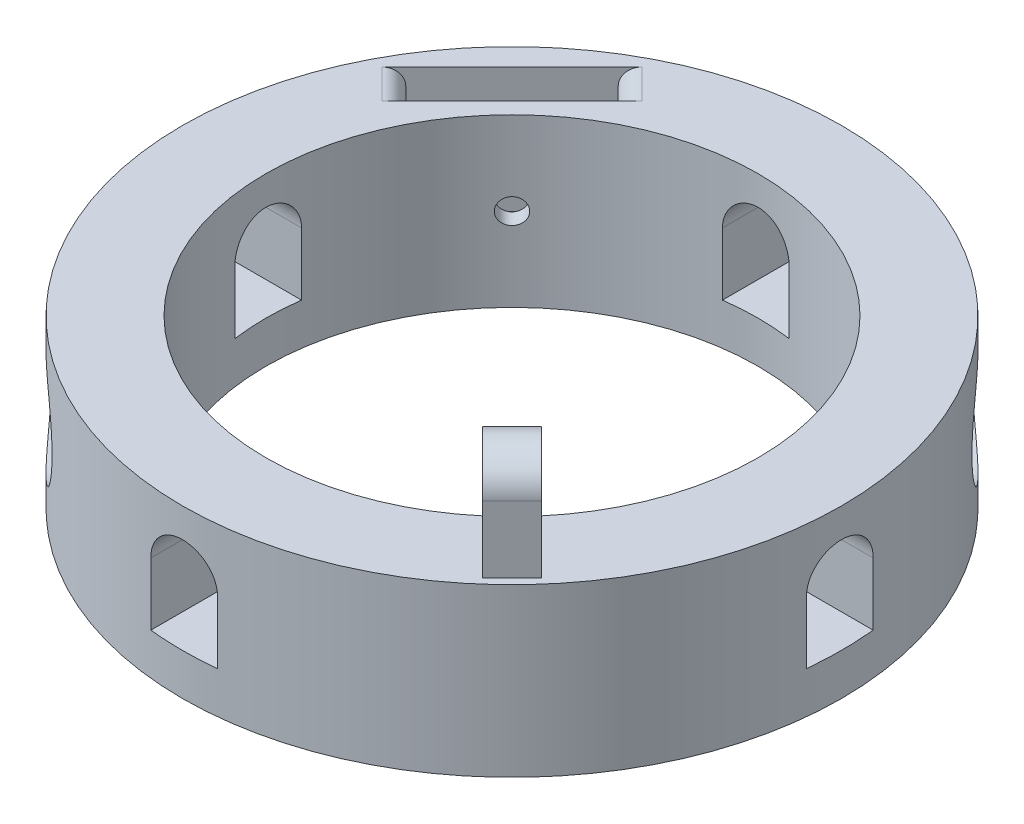
SolidWorks part; units mm, degrees
ref_plane "Front Plane" through (0, 0, 0) normal (0, 0, 1) x (1, 0, 0)
ref_plane "Top Plane" through (0, 0, 0) normal (0, 1, 0) x (1, 0, 0)
ref_plane "Right Plane" through (0, 0, 0) normal (1, 0, 0) x (0, 0, -1)
sketch "Sketch1" plane through (0, 0, 0) normal (0, 1, 0) x (1, 0, 0)
  circle A0 centre (0, 0) radius 29.5
  circle A1 centre (0, 0) radius 39.5
  dimension "D1" = 59
  dimension "D2" = 79
extrude "Boss-Extrude1" add sketch "Sketch1" along normal blind 20
ref_plane "Plane1" through (0, 0, 0) normal (0.7071, 0, -0.7071) x (-0.7071, 0, -0.7071)
sketch "Sketch2" plane through (0, 0, 0) normal (1, 0, 0) x (0, 0, -1)
  line L0 (0, 0) -> (0, 30.0667) construction
  line L1 (4, 5) -> (-4, 5)
  line L2 (-4, 5) -> (-4, 12.5)
  line L3 (4, 5) -> (4, 12.5)
  arc A0 (-4, 12.5) -> (4, 12.5) centre (0, 12.5) cw
  dimension "D6" = 4
  dimension "D1" = 8
  dimension "D2" = 4
  dimension "D3" = 5
  dimension "D4" = 7.5
  dimension "D5" = 7.5
extrude "Cut-Extrude1" cut sketch "Sketch2" against normal through all
extrude "Cut-Extrude2" cut sketch "Sketch2<2>" along normal through all
sketch "Sketch2<2>" plane through (0, 0, 0) normal (1, 0, 0) x (0, 0, -1) same geometry as "Sketch2"
mirror "Mirror1" about plane through (0, 0, 0) normal (0.7071, 0, -0.7071) of "Cut-Extrude2", "Cut-Extrude1"
sketch "Sketch4" plane through (0, 0, 0) normal (0.7071, 0, -0.7071) x (-0.7071, 0, -0.7071)
  line L0 (0, 0) -> (0, 44.1067) construction
  circle A0 centre (0, 10) radius 3.175
  dimension "D1" = 6.35
  dimension "D2" = 10
extrude "Cut-Extrude3" cut sketch "Sketch4" against normal up to next
extrude "Cut-Extrude4" cut sketch "Sketch4<2>" along normal up to next
sketch "Sketch4<2>" plane through (0, 0, 0) normal (0.7071, 0, -0.7071) x (-0.7071, 0, -0.7071) same geometry as "Sketch4"
ref_plane "Plane2" through (0, 0, 0) normal (0.7071, 0, 0.7071) x (0.7071, 0, -0.7071)
sketch "Sketch5" plane through (0, 20, 0) normal (0, 1, 0) x (1, 0, 0)
  line L0 (13.6827, -13.6827) -> (-13.6827, 13.6827) construction
  line L1 (-27.9307, 27.9307) -> (27.9307, -27.9307) construction
  line L2 (25.4558, -28.9914) -> (28.9914, -25.4558)
  line L3 (25.4558, -28.9914) -> (19.799, -23.3345)
  line L4 (28.9914, -25.4558) -> (23.3345, -19.799)
  line L5 (19.799, -23.3345) -> (23.3345, -19.799)
  line L6 (25.4558, -28.9914) -> (23.3345, -19.799) construction
  line L7 (28.9914, -25.4558) -> (19.799, -23.3345) construction
  circle A0 centre (0, 0) radius 39.5 construction
  circle A1 centre (0, 0) radius 29.5 construction
  point P7 (24.3952, -24.3952)
  dimension "D1" = 34.5
  dimension "D2" = 8
  dimension "D3" = 5
extrude "Boss-Extrude2" add sketch "Sketch5" along normal blind 13
sketch "Sketch6" plane through (1.7678, 0, -1.7678) normal (0.7071, 0, -0.7071) x (-0.7071, 0, -0.7071)
  line L0 (-38.5, 33) -> (-38.5, 20) construction
  line L1 (-38.5, 33) -> (-30.5, 33) construction
  line L2 (-30.5, 33) -> (-30.5, 20) construction
  line L4 (-38.5, 28) -> (-38.5, 33)
  line L8 (-38.5, 33) -> (-30.5, 33)
  line L9 (-30.5, 33) -> (-30.5, 28)
  arc A0 (-38.5, 28) -> (-30.5, 28) centre (-34.5, 28) cw
  dimension "D3" = 4
  dimension "D1" = 4
  dimension "D2" = 5
extrude "Cut-Extrude7" cut sketch "Sketch6" against normal up to next
sketch "Sketch7" plane through (1.7678, 0, -1.7678) normal (0.7071, 0, -0.7071) x (-0.7071, 0, -0.7071)
  circle A0 centre (-34.5, 28) radius 1
  dimension "D1" = 2
extrude "Cut-Extrude8" cut sketch "Sketch7" against normal up to next
ref_plane "Plane3" through (27.9307, 0, -27.9307) normal (0.7071, 0, -0.7071) x (-0.7071, 0, -0.7071)
sketch "Sketch8" plane through (27.9307, 0, -27.9307) normal (0.7071, 0, -0.7071) x (-0.7071, 0, -0.7071)
  circle A0 centre (0, 10) radius 6.35
  dimension "D1" = 12.7
extrude "Cut-Extrude9" cut sketch "Sketch8" against normal blind 1
mirror "Mirror3" about plane through (0, 0, 0) normal (0.7071, 0, -0.7071) of "Cut-Extrude9"
ref_plane "Plane4" through (0, 0, 0) normal (0.7071, 0, -0.7071) x (-0.7071, 0, -0.7071)
ref_plane "Plane5" through (0, 10, 0) normal (0, 1, 0) x (1, 0, 0)
ref_axis "Ball Join Axis" through (-41.2502, 10, -41.2502) along (0.7071, 0, 0.7071)
sketch "Sketch9" plane through (0, 20, 0) normal (0, 1, 0) x (1, 0, 0)
  line L2 (-19.4454, 32.1734) -> (-32.1734, 19.4454)
  line L3 (-15.9099, 28.6378) -> (-19.4454, 32.1734)
  line L4 (-28.6378, 15.9099) -> (-32.1734, 19.4454)
  line L5 (-41.2502, 41.2502) -> (45.8258, -45.8258) construction
  line L6 (-15.9099, 28.6378) -> (-28.6378, 15.9099)
  line L7 (-22.2739, 22.2739) -> (-25.8094, 25.8094) construction
  dimension "D3" = 5
  dimension "D4" = 31.5
  dimension "D1" = 18
extrude "Cut-Extrude11" cut sketch "Sketch9" against normal blind 15 contours L2 L4 L6 L3
sketch "Sketch10" plane through (0, 0, 0) normal (0.7071, 0, 0.7071) x (0.7071, 0, -0.7071)
  circle A0 centre (0, 10) radius 1.5
  dimension "D2" = 3
  dimension "D1" = 0
extrude "Cut-Extrude12" cut sketch "Sketch10" against normal blind 40
fillet "Fillet1" radius 2 1 edges at (-17.6777, 20, -30.4056)
fillet "Fillet2" radius 2 1 edges at (-30.4056, 20, -17.6777)
